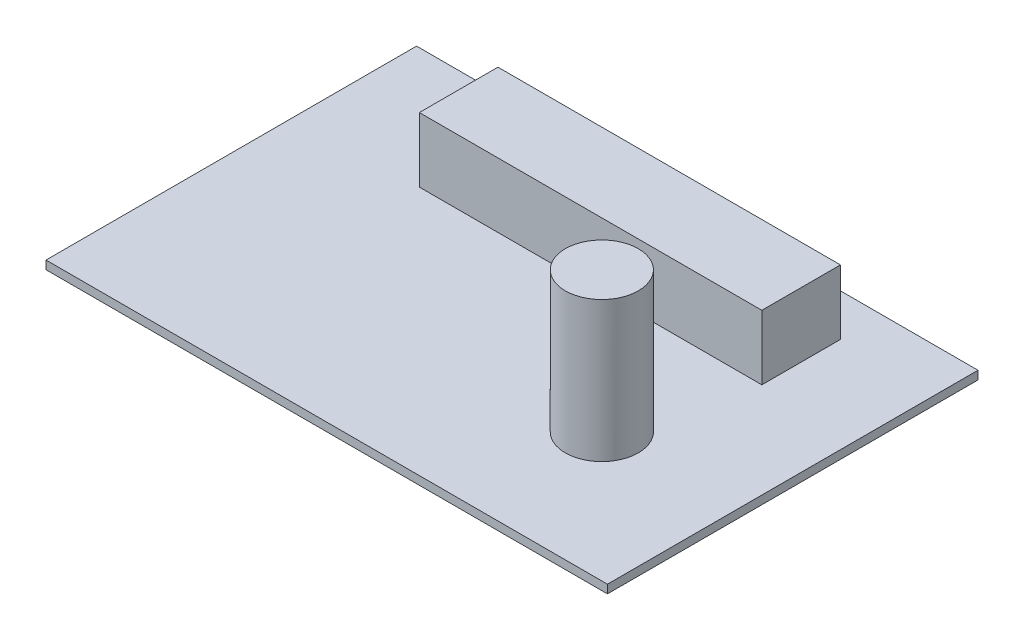
SolidWorks part; units mm, degrees
ref_plane "Ebene vorne" through (0, 0, 0) normal (0, 0, 1) x (1, 0, 0)
ref_plane "Ebene oben" through (0, 0, 0) normal (0, 1, 0) x (1, 0, 0)
ref_plane "Ebene rechts" through (0, 0, 0) normal (1, 0, 0) x (0, 0, -1)
sketch "Skizze1" plane through (0, 0, 0) normal (0, 1, 0) x (1, 0, 0)
  line L1 (-50, -33) -> (50, -33)
  line L2 (-50, -33) -> (-50, 33)
  line L3 (-50, 33) -> (50, 33)
  line L4 (50, -33) -> (50, 33)
  line L5 (-50, -33) -> (50, 33) construction
  line L6 (-50, 33) -> (50, -33) construction
  point P0 (0, 0)
  dimension "D1" = 100
  dimension "D2" = 66
extrude "Aufsatz-Linear austragen1" add sketch "Skizze1" along normal blind 1.5
sketch "Skizze2" plane through (0, 1.5, 0) normal (0, 1, 0) x (1, 0, 0)
  line L0 (50, 33) -> (-50, 33) construction
  line L1 (-28, 25.5) -> (33, 25.5)
  line L2 (-28, 25.5) -> (-28, 11.5)
  line L3 (-28, 11.5) -> (33, 11.5)
  line L4 (33, 25.5) -> (33, 11.5)
  line L5 (50, -33) -> (50, 33) construction
  dimension "D1" = 61
  dimension "D2" = 14
  dimension "D3" = 7.5
  dimension "D4" = 17
extrude "Aufsatz-Linear austragen2" add sketch "Skizze2" along normal blind 11.5
sketch "Skizze3" plane through (0, 1.5, 0) normal (0, 1, 0) x (1, 0, 0)
  line L0 (50, -33) -> (50, 33) construction
  line L1 (-50, -33) -> (50, -33) construction
  circle A0 centre (26, -10) radius 6.5
  dimension "D1" = 13
  dimension "D2" = 24
  dimension "D3" = 23
extrude "Aufsatz-Linear austragen3" add sketch "Skizze3" along normal blind 25
